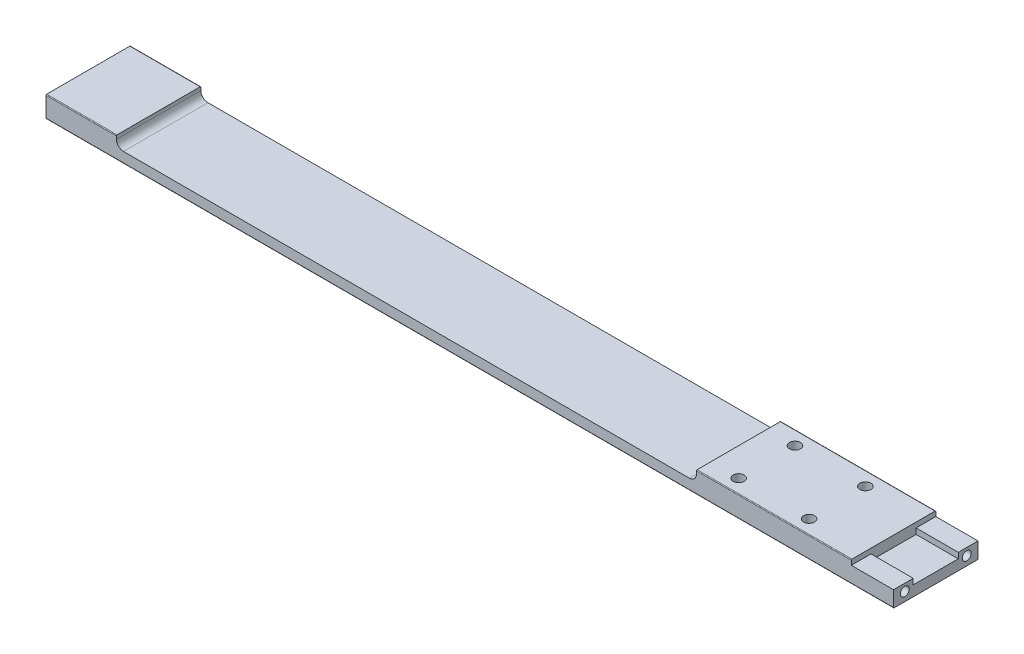
SolidWorks part; units mm, degrees
ref_plane "Front Plane" through (0, 0, 0) normal (0, 0, 1) x (1, 0, 0)
ref_plane "Top Plane" through (0, 0, 0) normal (0, 1, 0) x (1, 0, 0)
ref_plane "Right Plane" through (0, 0, 0) normal (1, 0, 0) x (0, 0, -1)
sketch "Sketch1" plane through (0, 0, 0) normal (0, 1, 0) x (1, 0, 0)
  line L1 (191.135, -19.05) -> (-191.135, -19.05)
  line L2 (191.135, -19.05) -> (191.135, 19.05)
  line L3 (191.135, 19.05) -> (-191.135, 19.05)
  line L4 (-191.135, -19.05) -> (-191.135, 19.05)
  line L5 (191.135, -19.05) -> (-191.135, 19.05) construction
  line L6 (191.135, 19.05) -> (-191.135, -19.05) construction
  point P0 (0, 0)
  dimension "Length" = 382.27
  dimension "Width" = 38.1
sketch "Sketch2" plane through (0, 0, 0) normal (1, 0, 0) x (0, 0, -1)
  line L0 (19.05, 4.7625) -> (19.05, -4.7625) construction
  point P2 (19.05, 0)
  dimension "Thickness" = 9.525
sketch "Sketch3" plane through (0, 0, 0) normal (0, 1, 0) x (1, 0, 0)
  line L1 (-191.135, 19.05) -> (191.135, 19.05)
  line L2 (-191.135, 19.05) -> (-191.135, -19.05)
  line L3 (-191.135, -19.05) -> (191.135, -19.05)
  line L4 (191.135, 19.05) -> (191.135, -19.05)
extrude "Boss-Extrude1" add sketch "Sketch3" against normal up to vertex (4.7625 mm away) and the other way up to vertex (4.7625 mm away) up to point (0, -4.7625, -19.05) other way up to point (0, 4.7625, -19.05)
fillet "Fillet1" radius 0.3143 4 edges at (0, -4.7625, 19.05) (0, -4.7625, -19.05) (0, 4.7625, -19.05) (0, 4.7625, 19.05)
sketch "Sketch4" plane through (-191.135, 0, 0) normal (-1, 0, 0) x (0, 0, 1)
  line L0 (0, -0.762) -> (13.97, -0.762) construction
  line L1 (0, -0.762) -> (-13.97, -0.762) construction
  line L2 (0, -0.762) -> (0, 0) construction
  dimension "D1" = 13.97
  dimension "D2" = 13.97
  dimension "D3" = 0.762
hole_wizard "Tap Drill for #10-32 Tap1" positions "Sketch5" profile "Sketch6" hole size "#10-32" standard "ANSI Inch"
sketch "Sketch5" plane through (-191.135, 0, 0) normal (-1, 0, 0) x (0, 0, 1)
  point P0 (-13.97, -0.762)
  point P3 (13.97, -0.762)
sketch "Sketch6" plane through (-191.135, -0.762, -13.97) normal (0, 1, 0) x (0, 0, 1)
  line L0 (0, 0) -> (0, 26.6133)
  line L1 (0, 26.6133) -> (2.0193, 25.4)
  line L2 (2.0193, 25.4) -> (2.0193, 0)
  line L5 (2.0193, 0) -> (0, 0)
  line L10 (0, 26.6133) -> (-2.0193, 25.4) construction
  line L11 (0, -6.35) -> (0, 107.95) construction
  dimension "Hole Dia." = 4.0386
  dimension "Hole Depth" = 25.4
  dimension "Drill Angle" = 118
hole_wizard "Tap Drill for #10-32 Tap2" positions "Sketch7" profile "Sketch8" hole size "#10-32" standard "ANSI Inch"
sketch "Sketch7" plane through (191.135, 0, 0) normal (1, 0, 0) x (0, 0, -1)
  point P0 (-13.97, -0.762)
  point P3 (13.97, -0.762)
sketch "Sketch8" plane through (191.135, -0.762, 13.97) normal (0, 1, 0) x (0, 0, -1)
  line L0 (0, 0) -> (0, 26.6133)
  line L1 (0, 26.6133) -> (2.0193, 25.4)
  line L2 (2.0193, 25.4) -> (2.0193, 0)
  line L5 (2.0193, 0) -> (0, 0)
  line L10 (0, 26.6133) -> (-2.0193, 25.4) construction
  line L11 (0, -6.35) -> (0, 107.95) construction
  dimension "Hole Dia." = 4.0386
  dimension "Hole Depth" = 25.4
  dimension "Drill Angle" = 118
sketch "Sketch10" plane through (0, 0, -19.05) normal (0, 0, -1) x (-1, 0, 0)
  line L0 (159.385, 4.7625) -> (159.385, 3.175)
  line L1 (-191.135, 4.7625) -> (191.135, 4.7625) construction
  line L2 (156.21, 0) -> (-99.06, 0)
  line L3 (-102.235, 3.175) -> (-102.235, 4.7625)
  line L4 (-102.235, 4.7625) -> (159.385, 4.7625)
  line L5 (-191.135, -4.7625) -> (-191.135, 78.8029) construction
  line L6 (191.135, -4.7625) -> (191.135, 78.8029) construction
  line L7 (-191.135, 4.7625) -> (-172.085, 4.7625)
  line L8 (-172.085, 4.7625) -> (-172.085, 2.4765)
  line L9 (-172.085, 2.4765) -> (-191.135, 2.4765)
  line L10 (-191.135, -4.4482) -> (-191.135, 4.4482) construction
  line L11 (-191.135, 2.4765) -> (-191.135, 4.7625)
  arc A0 (159.385, 3.175) -> (156.21, 0) centre (156.21, 3.175) cw
  arc A1 (-99.06, 0) -> (-102.235, 3.175) centre (-99.06, 3.175) cw
  point P12 (159.385, 0)
  dimension "D4" = 3.175
  dimension "D1" = 88.9
  dimension "D2" = 31.75
  dimension "D3" = 4.7625
  dimension "D5" = 19.05
  dimension "D6" = 2.286
extrude "Cut-Extrude1" cut sketch "Sketch10" against normal through all
sketch "Sketch13" plane through (0, -4.7625, 0) normal (0, -1, 0) x (1, 0, 0)
  line L0 (191.135, 0) -> (146.685, 0) construction
  line L1 (191.135, 18.7357) -> (191.135, -18.7357) construction
  line L2 (146.685, 0) -> (146.685, 12.7) construction
  line L3 (146.685, 12.7) -> (114.935, 12.7) construction
  line L4 (114.935, 12.7) -> (114.935, -12.7) construction
  line L5 (114.935, -12.7) -> (146.685, -12.7) construction
  line L6 (146.685, -12.7) -> (146.685, 0) construction
  dimension "D1" = 44.45
  dimension "D2" = 31.75
  dimension "D3" = 31.75
hole_wizard "#10 Clearance Hole1" positions "Sketch14" profile "Sketch15" hole size "#10" standard "ANSI Inch" end condition through all
sketch "Sketch14" plane through (0, -4.7625, 0) normal (0, -1, 0) x (-1, 0, 0)
  point P0 (-114.935, 12.7)
  point P3 (-146.685, 12.7)
  point P6 (-146.685, -12.7)
  point P9 (-114.935, -12.7)
sketch "Sketch15" plane through (114.935, -4.7625, -12.7) normal (1, 0, 0) x (0, 0, -1)
  line L0 (0, 0) -> (0, 9.525)
  line L1 (0, 9.525) -> (2.4892, 9.525)
  line L2 (2.4892, 9.525) -> (2.4892, 3.1411)
  line L3 (2.4892, 3.1411) -> (5.2197, 0)
  line L5 (5.2197, 0) -> (0, 0)
  line L6 (-2.4892, 3.1411) -> (-5.2197, 0) construction
  line L11 (0, -6.35) -> (0, 107.95) construction
  dimension "Thru Hole Dia." = 4.9784
  dimension "Thru Hole Depth" = 9.525
  dimension "Near C'Sink Dia." = 10.4394
  dimension "Near C'Sink Angle" = 82
sketch "Sketch17" plane through (0, 2.4765, 0) normal (0, 1, 0) x (1, 0, 0)
  line L23 (191.135, 0) -> (191.135, 10.16)
  line L24 (191.135, -19.05) -> (191.135, 19.05) construction
  line L25 (191.135, 10.16) -> (172.085, 10.16)
  line L26 (172.085, -19.05) -> (172.085, 19.05) construction
  line L27 (172.085, 10.16) -> (172.085, -10.16)
  line L28 (172.085, -10.16) -> (191.135, -10.16)
  line L29 (191.135, -10.16) -> (191.135, 0)
extrude "Cut-Extrude2" cut sketch "Sketch17" against normal blind 2.54
equation "\"D1@Fillet1\" = \"Thickness@Sketch2\" * .033"
